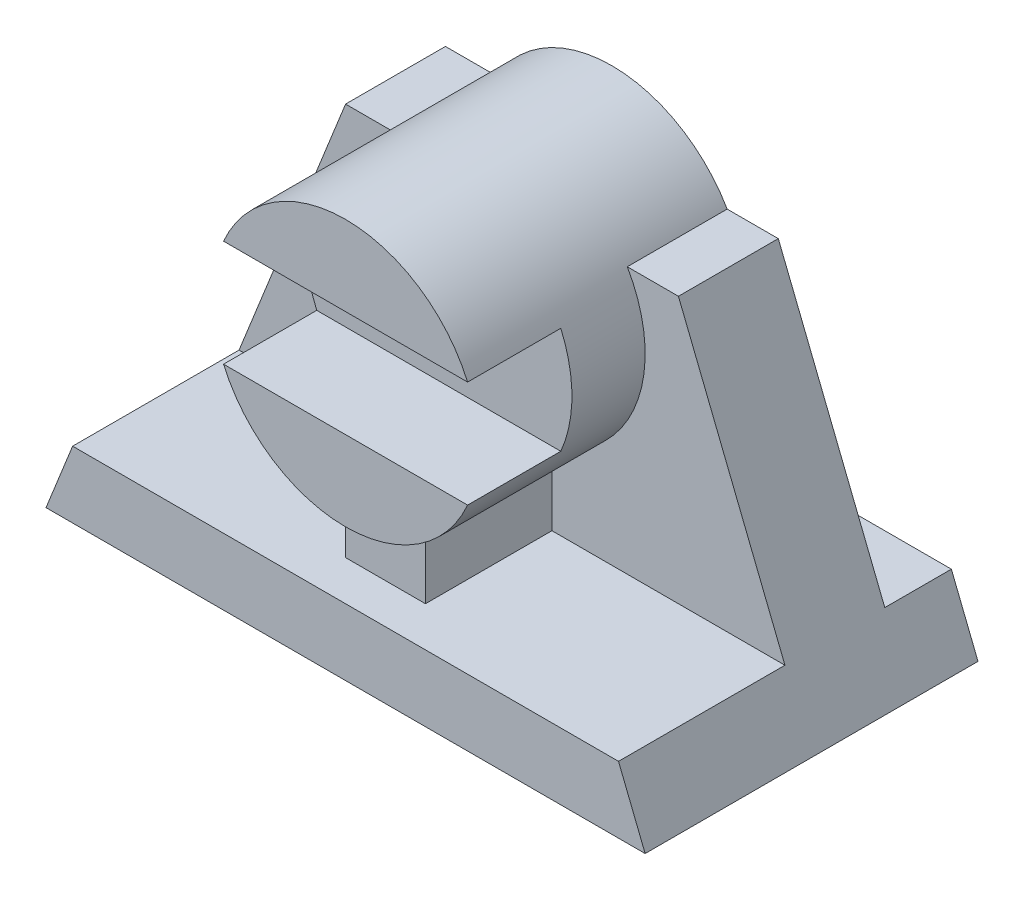
SolidWorks part; units mm, degrees
ref_plane "Front Plane" through (0, 0, 0) normal (0, 0, 1) x (1, 0, 0)
ref_plane "Top Plane" through (0, 0, 0) normal (0, 1, 0) x (1, 0, 0)
ref_plane "Right Plane" through (0, 0, 0) normal (1, 0, 0) x (0, 0, -1)
sketch "Sketch1" plane through (0, 0, 0) normal (0, 0, 1) x (1, 0, 0)
  line L0 (-64.6963, -32.477) -> (25.3037, -32.477)
  line L1 (-64.6963, -32.477) -> (-44.6963, -32.477)
  line L3 (-44.6963, 17.523) -> (-37.0168, 17.523)
  line L4 (5.3037, 17.523) -> (25.3037, -32.477)
  line L5 (-44.6963, 17.523) -> (-64.6963, -32.477)
  line L6 (-64.6963, -32.477) -> (-25.6963, -32.477)
  line L7 (-60.6963, -22.477) -> (21.3037, -22.477)
  line L8 (-25.6963, -22.477) -> (-25.6963, -11.5558)
  line L9 (-25.6963, -32.477) -> (-13.6963, -32.477)
  line L10 (-13.6963, -22.477) -> (-13.6963, -11.5558)
  line L11 (-2.3758, 17.523) -> (5.3037, 17.523)
  circle A0 centre (-19.6963, 7.523) radius 20
extrude "Boss-Extrude1" add sketch "Sketch1" along normal blind 40 and the other way blind 10 contours L7 L5 L0 L4 region at (-19.6963, -27.5545, 0)
extrude "Boss-Extrude2" add sketch "Sketch1<3>" along normal blind 15 contours A0 L10 L7 L4 L3 | A0 L3 L5 L7 L8 region at (-42.9706, -8.5065, 0) region at (3.578, -8.5065, 0)
sketch "Sketch1<3>" plane through (0, 0, 0) normal (0, 0, 1) x (1, 0, 0) same geometry as "Sketch1"
extrude "Boss-Extrude3" add sketch "Sketch1<4>" along normal blind 34 contours A0 L8 L7 L10 region at (-19.6963, -17.3213, 0)
sketch "Sketch1<4>" plane through (0, 0, 0) normal (0, 0, 1) x (1, 0, 0) same geometry as "Sketch1"
extrude "Boss-Extrude4" add sketch "Sketch1<6>" along normal blind 40 contours A0 region at (-19.6963, 7.523, 0)
sketch "Sketch1<6>" plane through (0, 0, 0) normal (0, 0, 1) x (1, 0, 0) same geometry as "Sketch1"
sketch "Sketch2" plane through (0, 0, 40) normal (0, 0, 1) x (1, 0, 0)
  line L0 (-39.6963, 7.523) -> (0.3037, 7.523) construction
  line L1 (-39.6963, 15.523) -> (0.3037, 15.523)
  line L2 (-39.6963, -0.477) -> (0.3037, -0.477)
  arc A0 (-13.6963, -11.5558) -> (-2.3758, 17.523) centre (-19.6963, 7.523) ccw construction
  arc A1 (-39.6963, 15.523) -> (-39.6963, -0.477) centre (-39.6963, 7.523) ccw
  arc A2 (0.3037, -0.477) -> (0.3037, 15.523) centre (0.3037, 7.523) ccw
  point P6 (-19.6963, 7.523)
extrude "Cut-Extrude1" cut sketch "Sketch2" against normal blind 14
